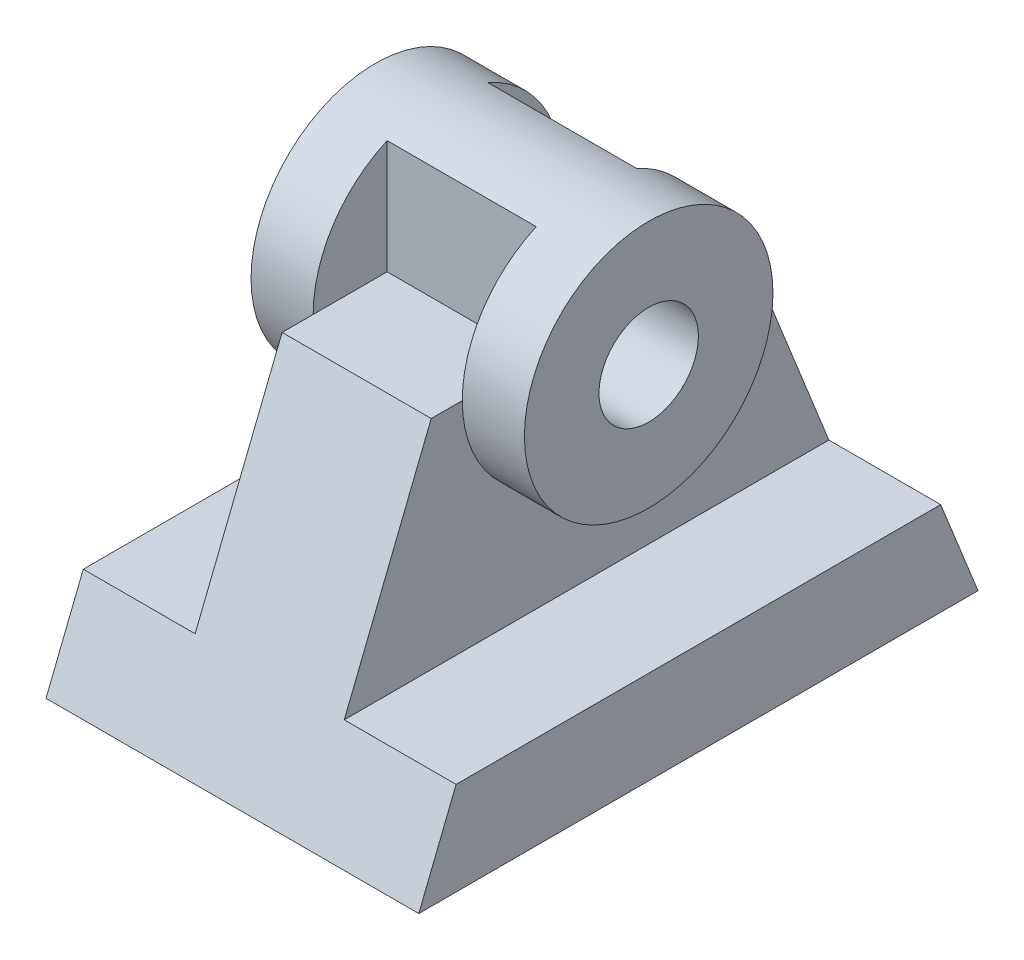
SolidWorks part; units mm, degrees
ref_plane "Alzado" through (0, 0, 0) normal (0, 0, 1) x (1, 0, 0)
ref_plane "Planta" through (0, 0, 0) normal (0, 1, 0) x (1, 0, 0)
ref_plane "Vista lateral" through (0, 0, 0) normal (1, 0, 0) x (0, 0, -1)
sketch "Croquis1" plane through (0, 0, 0) normal (1, 0, 0) x (0, 0, -1)
  line L0 (0, 43.9058) -> (0, -43.9058) construction
  line L1 (45, -25) -> (-45, -25)
  line L2 (-45, -25) -> (-25, 25)
  line L3 (-25, 25) -> (25, 25)
  line L4 (45, -25) -> (25, 25)
  point P2 (0, 0)
  point P8 (35, 0)
  point P9 (0, -25)
  point P10 (0, 25)
  dimension "D1" = 90
  dimension "D2" = 50
  dimension "D3" = 50
extrude "Saliente-Extruir1" add sketch "Croquis1" against normal mid plane 60
ref_plane "Plano1" through (0, 0, 45) normal (0, 0, 1) x (1, 0, 0)
sketch "Croquis2" plane through (0, 0, 45) normal (0, 0, 1) x (1, 0, 0)
  line L0 (0, 25) -> (0, -25) construction
  line L1 (-30, 25) -> (30, 25) construction
  line L2 (-30, -25) -> (30, -25) construction
  line L3 (-30, 25) -> (-30, -25) construction
  line L4 (-30, -10) -> (-12, -10)
  line L5 (-30, -10) -> (-30, 25)
  line L6 (-30, 25) -> (-12, 25)
  line L7 (-12, -10) -> (-12, 25)
  line L8 (30, 25) -> (12, 25)
  line L9 (12, -10) -> (12, 25)
  line L10 (30, -10) -> (12, -10)
  line L11 (30, -10) -> (30, 25)
  dimension "D1" = 35
  dimension "D2" = 24
extrude "Cortar-Extruir1" cut sketch "Croquis2" against normal through all
sketch "Croquis3" plane through (0, 0, 0) normal (1, 0, 0) x (0, 0, -1)
  line L0 (25, 25) -> (-25, 25) construction
  circle A0 centre (0, 25) radius 20
  circle A1 centre (0, 25) radius 8
  dimension "D1" = 40
  dimension "D2" = 16
extrude "Saliente-Extruir3" add sketch "Croquis3" along normal mid plane 44 contours A0
extrude "Cortar-Extruir2" cut sketch "Croquis3<4>" against normal mid plane 44 contours A1
sketch "Croquis3<4>" plane through (0, 0, 0) normal (1, 0, 0) x (0, 0, -1) same geometry as "Croquis3"
ref_plane "Plano2" through (0, 45, 0) normal (0, 1, 0) x (1, 0, 0)
sketch "Croquis4" plane through (0, 45, 0) normal (0, 1, 0) x (1, 0, 0)
  line L0 (-22, 0) -> (22, 0) construction
  line L1 (-12, 20) -> (12, 20)
  line L2 (-12, 20) -> (-12, 8.1)
  line L3 (-12, 8.1) -> (12, 8.1)
  line L4 (12, 20) -> (12, 8.1)
  line L5 (-22, 20) -> (-22, -20) construction
  line L6 (22, -20) -> (22, 20) construction
  line L7 (-12, -8.1) -> (12, -8.1)
  line L8 (12, -20) -> (12, -8.1)
  line L9 (-12, -20) -> (12, -20)
  line L10 (-12, -20) -> (-12, -8.1)
  dimension "D1" = 24
  dimension "D2" = 16.2
extrude "Cortar-Extruir6" cut sketch "Croquis4" against normal up to surface (20 mm away) up to face at (0, 25, 22.5)
